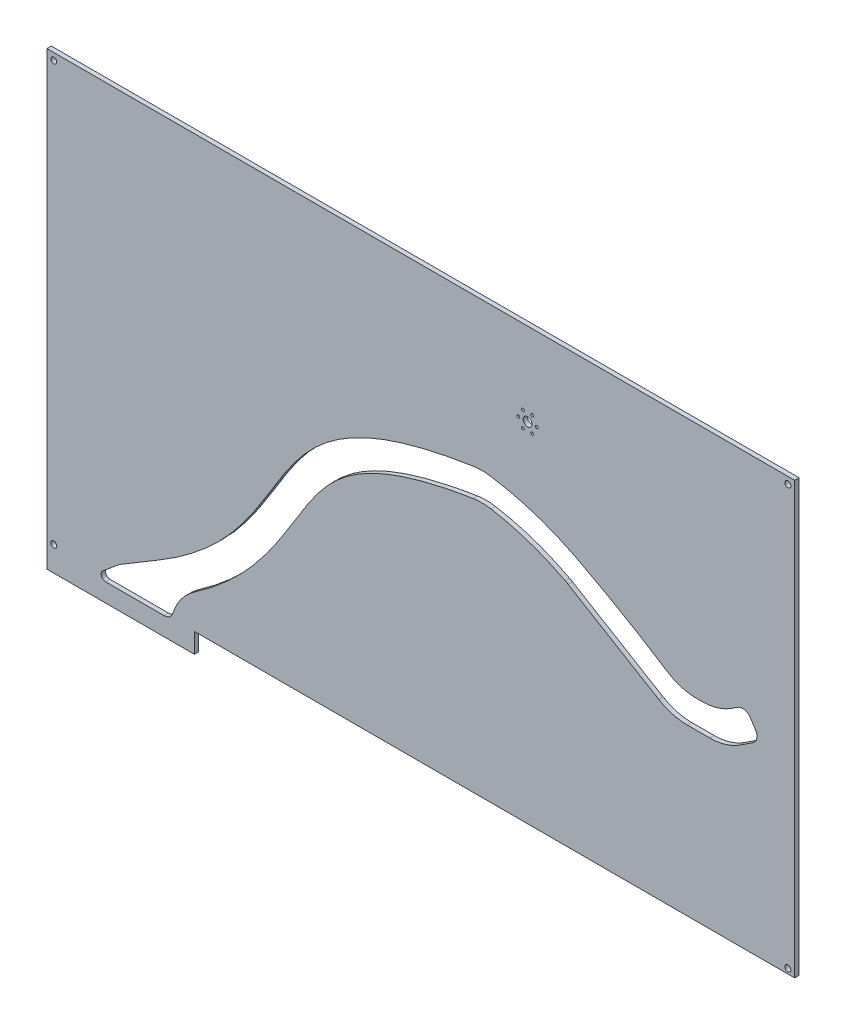
SolidWorks part; units mm, degrees
ref_plane "前视基准面" through (0, 0, 0) normal (0, 0, 1) x (1, 0, 0)
ref_plane "上视基准面" through (0, 0, 0) normal (0, 1, 0) x (1, 0, 0)
ref_plane "右视基准面" through (0, 0, 0) normal (1, 0, 0) x (0, 0, -1)
sketch "Sketch1" plane through (0, 0, 0) normal (0, 0, 1) x (1, 0, 0)
  line L0 (86.3892, 46.5642) -> (136.3892, 46.5642) construction
  line L1 (136.3892, 46.5642) -> (169.6686, 68.4983) construction
  line L2 (-475, -100) -> (-518.0311, -125.7444)
  line L3 (-436.8168, -147.9944) -> (-436.8168, -169.5504)
  line L4 (81.7745, 31.5642) -> (140.8878, 31.5642)
  line L5 (-467.2989, -112.8722) -> (-510.33, -138.6166) construction
  line L6 (140.8878, 31.5642) -> (177.9233, 55.9739)
  line L7 (-459.5978, -125.7444) -> (-459.5978, -149.5504)
  line L8 (-436.8168, -147.9944) -> (215.0808, -147.9944)
  line L9 (215.0808, -147.9944) -> (215.0808, 320)
  line L10 (215.0808, 320) -> (-596.8168, 320)
  line L11 (-596.8168, -150) -> (-596.8168, 320)
  line L12 (215.0808, -147.9944) -> (-596.8168, 320) construction
  line L13 (215.0808, 320) -> (-596.8168, -150) construction
  line L14 (-518.0311, -125.7444) -> (-459.5978, -125.7444) construction
  line L15 (-459.5978, -149.5504) -> (-546.7804, -149.5504)
  line L16 (-546.7804, -149.5504) -> (-518.0311, -125.7444)
  line L17 (90.9712, 61.5642) -> (131.8907, 61.5642)
  line L18 (-436.8168, -169.5504) -> (-596.8168, -169.5504)
  line L19 (-596.8168, -169.5504) -> (-596.8168, -150)
  line L21 (-32.3237, 100) -> (135.1953, 100) construction
  line L22 (-25, 130) -> (125, 130) construction
  line L23 (-28.6108, 115) -> (130.0228, 115) construction
  line L24 (131.8907, 61.5642) -> (161.4139, 81.0227)
  line L25 (177.9233, 55.9739) -> (161.4139, 81.0227)
  line L26 (-21.7014, 128.3139) -> (-25, 130)
  line L27 (-32.3237, 100) -> (81.7745, 31.5642)
  arc A0 (-125, 160) -> (-25, 130) centre (-159.8893, -137.9643) cw
  arc A1 (-28.6108, 115) -> (86.3892, 46.5642) centre (-559.3589, -907.7137) cw construction
  arc A2 (-124.7147, 129.7347) -> (-32.3237, 100) centre (-159.8893, -137.9643) cw
  circle A3 centre (-75, 230) radius 10 construction
  arc A4 (-124.84, 144.8723) -> (-28.6108, 115) centre (-159.8893, -137.9643) cw construction
  arc A5 (-21.7014, 128.3139) -> (90.9712, 61.5642) centre (-559.3589, -907.7137) cw
  circle A6 centre (-589.3757, -142.5578) radius 3.2924
  circle A7 centre (207.6422, -142.5578) radius 3.2924
  circle A8 centre (207.6422, 312.5578) radius 3.2944
  circle A9 centre (-589.3757, 312.5578) radius 3.1635
  arc A10 (135.1953, 100) -> (187.8618, 132.897) centre (303.6181, -111.0302) cw construction
  arc A11 (130.0228, 115) -> (181.4309, 146.4485) centre (303.6181, -111.0302) cw construction
  arc A12 (125, 130) -> (175, 160) centre (303.6181, -111.0302) cw construction
  arc A13 (-35.5202, 101.6861) -> (81.7745, 31.5642) centre (-559.3589, -907.7137) cw construction
  circle A14 centre (-85, 230) radius 1.5
  circle A15 centre (-80, 238.6603) radius 1.5
  circle A16 centre (-70, 238.6603) radius 1.5
  circle A17 centre (-65, 230) radius 1.5
  circle A18 centre (-70, 221.3397) radius 1.5
  circle A19 centre (-80, 221.3397) radius 1.5
  circle A20 centre (-75, 230) radius 4.7625
  spline S0 degree 3 poles (-475, -100) (-419.5406, -66.8201) (-329.5908, 43.116) (-307.6356, 134.2871) (-125, 160) knots 0 0 0 0 0.312224 1 1 1 1
  spline S1 degree 1 poles (-459.5978, -125.7444) (-124.7147, 129.7347) knots 0 0 1 1 construction
  spline S2 degree 3 poles (-459.5978, -125.7444) (-458.1292, -124.8657) (-455.1858, -123.0815) (-449.4714, -119.5247) (-442.5555, -115.0462) (-434.6362, -109.6397) (-424.5564, -102.3861) (-412.8294, -93.2453) (-400.0558, -82.1905) (-388.4865, -71.0922) (-374.5374, -56.3046) (-359.6201, -37.9792) (-344.8908, -16.7676) (-332.3401, 3.2457) (-321.0552, 21.7964) (-310.226, 38.6648) (-299.0796, 53.8348) (-286.8128, 67.5146) (-272.4318, 80.0885) (-257.6527, 89.9241) (-243.4982, 97.442) (-231.5651, 102.8866) (-218.1727, 108.1127) (-203.191, 113.0878) (-189.2817, 116.9961) (-177.2434, 119.9629) (-167.7458, 122.1041) (-157.766, 124.1573) (-149.0369, 125.7919) (-141.7993, 127.0518) (-136.2431, 127.9723) (-131.5022, 128.7191) (-127.6487, 129.3032) (-125.6903, 129.5925) (-124.7147, 129.7347) knots 0 0 0 0 0.007773 0.015545 0.03109 0.046636 0.062181 0.093271 0.124361 0.155452 0.186542 0.248723 0.310904 0.373084 0.435265 0.497446 0.559626 0.621807 0.683988 0.746169 0.777259 0.808349 0.83944 0.87053 0.90162 0.917166 0.932711 0.948256 0.963801 0.971574 0.979346 0.987119 0.991005 0.994892 0.994892 0.994892 0.994892
  spline S3 degree 1 poles (-467.2989, -112.8722) (-124.84, 144.8723) knots 0 0 1 1 construction
  spline S4 degree 3 poles (-467.2989, -112.8722) (-465.8766, -112.0213) (-463.025, -110.2926) (-457.4973, -106.8516) (-450.8174, -102.5249) (-443.1848, -97.3122) (-433.4896, -90.3317) (-422.2436, -81.559) (-410.0336, -70.981) (-398.9994, -60.3828) (-385.707, -46.2708) (-371.4731, -28.7597) (-357.2741, -8.2881) (-344.9599, 11.3612) (-333.6257, 29.9919) (-322.417, 47.4318) (-310.4985, 63.6121) (-297.0179, 78.5777) (-281.0248, 92.4603) (-264.7088, 103.2127) (-249.3105, 111.3089) (-236.4572, 117.1105) (-222.1723, 122.621) (-206.3349, 127.8161) (-191.7467, 131.8615) (-179.1859, 134.915) (-169.3063, 137.1107) (-158.9544, 139.2089) (-149.9221, 140.8739) (-142.4479, 142.1541) (-136.7117, 143.0887) (-130.8627, 143.9946) (-126.8382, 144.5862) (-124.84, 144.8723) knots 0 0 0 0 0.007793 0.015586 0.031173 0.046759 0.062345 0.093518 0.12469 0.155863 0.187036 0.249381 0.311726 0.374071 0.436417 0.498762 0.561107 0.623452 0.685798 0.748143 0.779315 0.810488 0.841661 0.872833 0.904006 0.919592 0.935179 0.950765 0.966351 0.974144 0.981937 0.989731 0.997524 0.997524 0.997524 0.997524 construction
  point P38 (-190, 85.5025)
  point P62 (-75, 230)
  dimension "D5" = 300
  dimension "D8" = 15
  dimension "D14" = 470
  dimension "D18" = 70
  dimension "D22" = 651.8975
  dimension "D24" = 50
  dimension "D26" = 6
  dimension "D27" = 3
  dimension "D28" = 9.525
  dimension "D29" = 20
  dimension "D1" = 105
  dimension "D2" = 100
  dimension "D3" = 350
  dimension "D4" = 260
  dimension "D6" = 100
  dimension "D7" = 30
  dimension "D9" = 15
  dimension "D10" = 115
  dimension "D11" = 50
  dimension "D13" = 15
  dimension "D15" = 190
  dimension "D16" = 320
  dimension "D17" = 20
  dimension "D25" = 811.9
  dimension "D12" = 30
extrude "Boss-Extrude1" add sketch "Sketch1" along normal blind 4.7625
fillet "Fillet1" radius 10 3 edges at (-459.5978, -149.5504, 2.3813) (161.4139, 81.0227, 2.3813) (177.9233, 55.9739, 2.3813)
fillet "Fillet2" radius 5 1 edges at (-546.7804, -149.5504, 2.3813)
fillet "Fillet3" radius 60 8 edges at (-125, 160, 2.3813) (-124.7147, 129.7347, 2.3813) (140.8878, 31.5642, 2.3813) (81.7745, 31.5642, 2.3813) (90.9712, 61.5642, 2.3813) (131.8907, 61.5642, 2.3813) (-32.3237, 100, 2.3813) (-459.5978, -125.7444, 2.3813)
